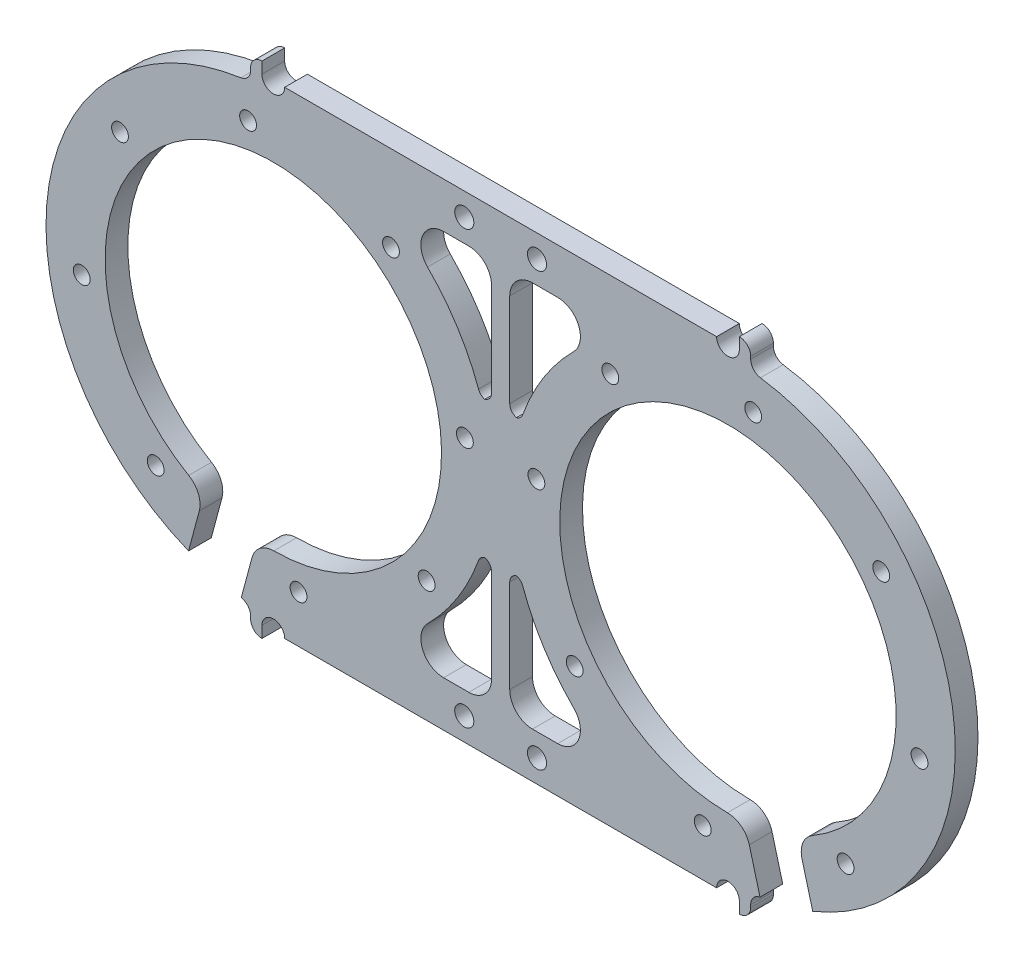
SolidWorks part; units mm, degrees
ref_plane "前视基准面" through (0, 0, 0) normal (0, 0, 1) x (1, 0, 0)
ref_plane "上视基准面" through (0, 0, 0) normal (0, 1, 0) x (1, 0, 0)
ref_plane "右视基准面" through (0, 0, 0) normal (1, 0, 0) x (0, 0, -1)
sketch "草图1" plane through (0, 0, 0) normal (0, 0, 1) x (1, 0, 0)
  line L1 (-50, 0) -> (-50, -42.5) construction
  line L2 (-55, 49.7494) -> (-55, 55)
  line L7 (-55, -49.7494) -> (-55, -55)
  line L8 (55, -55) -> (-55, -55)
  line L9 (-55, 55) -> (55, 55)
  line L10 (0, -55) -> (0, 55) construction
  line L11 (50, 0) -> (50, -42.5) construction
  line L12 (55, -49.7494) -> (55, -55)
  line L13 (55, 49.7494) -> (55, 55)
  line L14 (55, 0) -> (-55, 0) construction
  arc A1 (-50, -42.5) -> (-44.4526, -42.1364) centre (-50, 0) ccw construction
  circle A2 centre (-44.4526, -42.1364) radius 1.85
  circle A3 centre (-75.8724, -33.7175) radius 1.85
  circle A4 centre (-92.1364, -5.5474) radius 1.85
  circle A5 centre (-83.7175, 25.8724) radius 1.85
  circle A6 centre (-55.5474, 42.1364) radius 1.85
  circle A7 centre (-24.1276, 33.7175) radius 1.85
  circle A8 centre (-7.8636, 5.5474) radius 1.85
  circle A9 centre (-16.2825, -25.8724) radius 1.85
  circle A10 centre (-50, 0) radius 37
  arc A11 (-55, 49.7494) -> (-55, -49.7494) centre (-50, 0) ccw
  arc A12 (50, -42.5) -> (44.4526, -42.1364) centre (50, 0) cw construction
  arc A13 (55, 49.7494) -> (55, -49.7494) centre (50, 0) cw
  circle A14 centre (50, 0) radius 37
  circle A15 centre (16.2825, -25.8724) radius 1.85
  circle A16 centre (7.8636, 5.5474) radius 1.85
  circle A17 centre (24.1276, 33.7175) radius 1.85
  circle A18 centre (55.5474, 42.1364) radius 1.85
  circle A19 centre (83.7175, 25.8724) radius 1.85
  circle A20 centre (92.1364, -5.5474) radius 1.85
  circle A21 centre (75.8724, -33.7175) radius 1.85
  circle A22 centre (44.4526, -42.1364) radius 1.85
  circle A23 centre (8, 47.5) radius 2.1
  circle A25 centre (8, -47.5) radius 2.1
  circle A27 centre (-8, -47.5) radius 2.1
  circle A28 centre (-8, 47.5) radius 2.1
  point P23 (-50, 0)
  point P26 (50, 0)
  point P50 (0, 55)
  point P51 (0, -55)
  dimension "D1" = 8
extrude "凸台-拉伸1" add sketch "草图1" along normal blind 5
fillet "圆角1" radius 2.5 8 edges at (-55, -49.7494, 2.5) (-55, -55, 2.5) (55, -55, 2.5) (55, -49.7494, 2.5) (55, 49.7494, 2.5) (55, 55, 2.5) (-55, 55, 2.5) (-55, 49.7494, 2.5)
sketch "草图2" plane through (0, 0, 5) normal (0, 0, 1) x (1, 0, 0)
  line L0 (-52.5, 55) -> (-52.5, 52.5)
  line L1 (-52.5, 52.5) -> (52.5, 52.5)
  line L2 (2.75, 0) -> (-2.75, 0) construction
  line L3 (-52.5, -52.5) -> (52.5, -52.5)
  line L4 (-52.5, -55) -> (-52.5, -52.5)
  line L5 (0, -2.75) -> (0, 2.75) construction
  line L6 (52.5, -55) -> (52.5, -52.5)
  line L7 (52.5, 55) -> (52.5, 52.5)
  line L8 (-52.5, 55) -> (52.5, 55)
  line L9 (52.5, -55) -> (-52.5, -55)
  point P13 (0, -52.5)
  point P14 (0, 52.5)
extrude "切除-拉伸1" cut sketch "草图2" against normal blind 10
sketch "草图3" plane through (0, 0, 5) normal (0, 0, 1) x (1, 0, 0)
  line L2 (-65.2451, -33.7133) -> (-53.654, -36.8191)
  line L3 (-55.4631, -43.5707) -> (-57.1454, -49.8492)
  line L4 (-67.0542, -40.4649) -> (-68.7365, -46.7434)
  line L5 (-55.4631, -43.5707) -> (-53.654, -36.8191)
  line L7 (-67.0542, -40.4649) -> (-65.2451, -33.7133)
  line L8 (-68.7365, -46.7434) -> (-57.1454, -49.8492)
  line L10 (68.7365, -46.7434) -> (57.1454, -49.8492)
  line L11 (67.0542, -40.4649) -> (65.2451, -33.7133)
  line L12 (55.4631, -43.5707) -> (53.654, -36.8191)
  line L13 (67.0542, -40.4649) -> (68.7365, -46.7434)
  line L14 (55.4631, -43.5707) -> (57.1454, -49.8492)
  line L15 (65.2451, -33.7133) -> (53.654, -36.8191)
extrude "切除-拉伸2" cut sketch "草图3" against normal blind 10
fillet "圆角2" radius 5 4 edges at (65.2451, -33.7133, 2.5) (53.654, -36.8191, 2.5) (-53.654, -36.8191, 2.5) (-65.2451, -33.7133, 2.5)
sketch "草图4" plane through (0, 0, 5) normal (0, 0, 1) x (1, 0, 0)
  line L0 (0, -2.75) -> (0, 2.75) construction
  line L1 (-8, 42.5) -> (-27.6897, 42.5)
  line L2 (-8, 42.5) -> (-2, 42.5)
  line L3 (-2, 42.5) -> (-2, 15)
  line L4 (-2, 15) -> (-4.4039, 15)
  line L5 (2, 15) -> (4.4039, 15)
  line L6 (2, 42.5) -> (2, 15)
  line L7 (8, 42.5) -> (2, 42.5)
  line L8 (8, 42.5) -> (27.6897, 42.5)
  line L9 (2.75, 0) -> (-2.75, 0) construction
  line L10 (8, -42.5) -> (27.6897, -42.5)
  line L11 (8, -42.5) -> (2, -42.5)
  line L12 (2, -42.5) -> (2, -15)
  line L13 (2, -15) -> (4.4039, -15)
  line L14 (-2, -15) -> (-4.4039, -15)
  line L15 (-2, -42.5) -> (-2, -15)
  line L16 (-8, -42.5) -> (-2, -42.5)
  line L17 (-8, -42.5) -> (-27.6897, -42.5)
  arc A0 (-4.4039, 15) -> (-27.6897, 42.5) centre (-50, 0) ccw
  arc A1 (4.4039, 15) -> (27.6897, 42.5) centre (50, 0) cw
  arc A2 (4.4039, -15) -> (27.6897, -42.5) centre (50, 0) ccw
  arc A3 (-4.4039, -15) -> (-27.6897, -42.5) centre (-50, 0) cw
extrude "切除-拉伸3" cut sketch "草图4" against normal blind 10
fillet "圆角3" radius 5 8 edges at (2, -42.5, 2.5) (-2, -42.5, 2.5) (-27.6897, -42.5, 2.5) (27.6897, -42.5, 2.5) (27.6897, 42.5, 2.5) (2, 42.5, 2.5) (-2, 42.5, 2.5) (-27.6897, 42.5, 2.5)
fillet "圆角4" radius 2 8 edges at (-2, -15, 2.5) (-4.4039, -15, 2.5) (4.4039, -15, 2.5) (2, -15, 2.5) (4.4039, 15, 2.5) (2, 15, 2.5) (-2, 15, 2.5) (-4.4039, 15, 2.5)
sketch "草图5" plane through (0, 0, 5) normal (0, 0, 1) x (1, 0, 0)
  line L0 (-52.5, 52.5) -> (-47.5, 52.5)
  line L1 (-52.5, 52.5) -> (52.5, 52.5) construction
  line L2 (0, -2.75) -> (0, 2.75) construction
  line L3 (52.5, 52.5) -> (47.5, 52.5)
  line L4 (2.75, 0) -> (-2.75, 0) construction
  line L5 (52.5, -52.5) -> (47.5, -52.5)
  line L6 (-52.5, -52.5) -> (-47.5, -52.5)
  arc A0 (-52.5, 52.5) -> (-47.5, 52.5) centre (-50, 52.5) ccw
  arc A1 (52.5, 52.5) -> (47.5, 52.5) centre (50, 52.5) cw
  arc A2 (52.5, -52.5) -> (47.5, -52.5) centre (50, -52.5) ccw
  arc A3 (-52.5, -52.5) -> (-47.5, -52.5) centre (-50, -52.5) cw
extrude "切除-拉伸4" cut sketch "草图5" against normal blind 10 contours L0 A0 | A1 L3 | L5 A2 | A3 L6 region at (-50, 51.439, 5) region at (50, 51.439, 5) region at (50, -51.439, 5) region at (-50, -51.439, 5)
